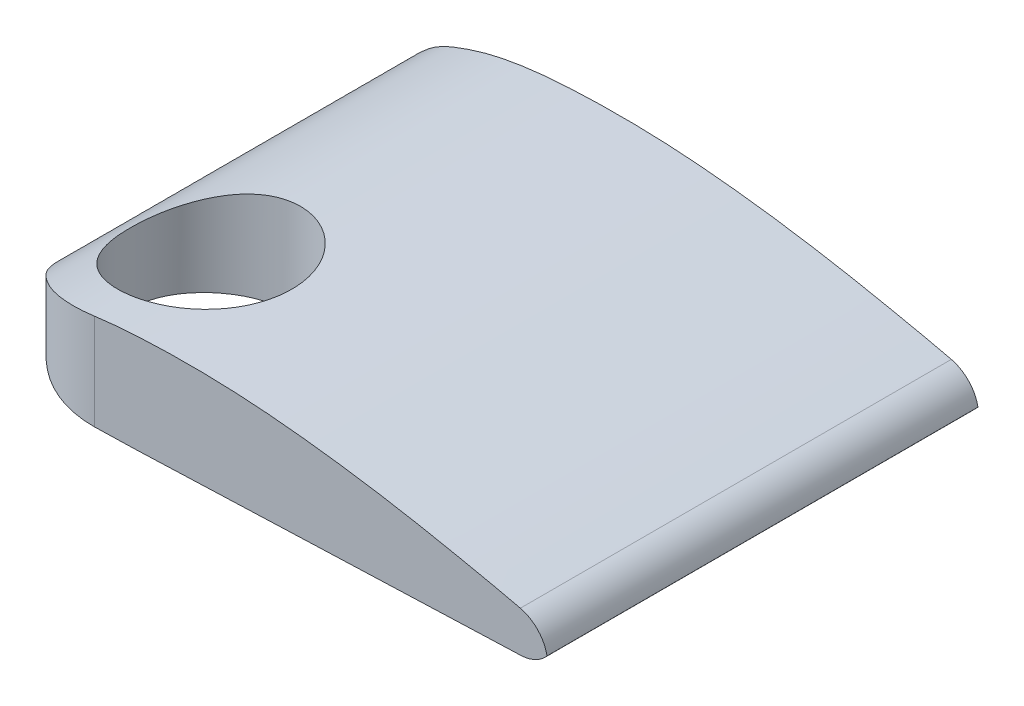
SolidWorks part; units mm, degrees
ref_plane "Ön Düzlem" through (0, 0, 0) normal (0, 0, 1) x (1, 0, 0)
ref_plane "Üst Düzlem" through (0, 0, 0) normal (0, 1, 0) x (1, 0, 0)
ref_plane "Sağ Düzlem" through (0, 0, 0) normal (1, 0, 0) x (0, 0, -1)
sketch "Sketch1" plane through (0, 0, 0) normal (0, 0, 1) x (1, 0, 0)
  line L0 (273.8644, 129.7584) -> (1369.8644, 129.7584) construction
  line L1 (149.8581, 0) -> (149.8558, -0.0087)
  line L2 (155.9643, 3.5657) -> (153.7663, -4.8024)
  spline S0 degree 3 poles (149.8581, 0) (148.0649, 0.471) (143.2248, 1.7424) (133.1757, 3.886) (119.4995, 6.7583) (102.5414, 9.7444) (85.9645, 11.9563) (70.8168, 13.3138) (56.6678, 13.8481) (41.7647, 13.6427) (27.8783, 12.5388) (17.5169, 10.3502) (10.936, 8.1212) (5.6282, 6.0173) (2.2408, 3.1599) (-0.2937, 0.7197) (0.5423, -2.4008) (4.9566, -3.5377) (10.6122, -4.3278) (18.7708, -4.4982) (30.5005, -4.4934) (45.7845, -3.9122) (66.3708, -3.1228) (87.0163, -2.3781) (108.488, -1.5762) (124.5472, -1.0028) (137.7849, -0.5219) (145.1223, -0.2664) (148.9169, -0.06) (149.8558, -0.0087) knots 0 0 0 0 0.018163 0.049023 0.100644 0.15508 0.217678 0.264436 0.304025 0.356345 0.410393 0.440307 0.459596 0.478843 0.494821 0.504999 0.508601 0.524256 0.542616 0.567477 0.602874 0.658123 0.717036 0.804816 0.860487 0.927555 0.96225 0.990269 0.999481 0.999481 0.999481 0.999481
  spline S1 degree 1 poles (155.9643, 3.5657) (153.7663, -4.8024) knots 0 0 1 1 construction
  spline S2 degree 3 poles (155.9643, 3.5657) (154.3789, 3.9821) (151.2214, 4.8106) (146.4053, 6.0796) (141.4592, 7.231) (136.6165, 8.2623) (131.8023, 9.2806) (125.348, 10.622) (117.2296, 12.2227) (107.436, 13.9393) (97.5987, 15.4408) (87.7223, 16.7063) (77.8097, 17.7331) (67.8079, 18.447) (57.7939, 18.7732) (47.7698, 18.7355) (39.4274, 18.4012) (32.6805, 17.8783) (27.5943, 17.2987) (22.4892, 16.4892) (18.2218, 15.5713) (14.817, 14.6458) (12.3108, 13.8604) (9.8671, 13.0078) (7.4153, 12.102) (5.1995, 11.1503) (3.4062, 10.1987) (2.0681, 9.3602) (0.8539, 8.4728) (-0.2716, 7.5539) (-1.1738, 6.7528) (-1.8463, 6.1385) (-2.5103, 5.5088) (-3.2938, 4.6501) (-4.14, 3.4467) (-4.7575, 1.9999) (-5.006, 0.5771) (-5.0045, -0.9474) (-4.6414, -2.46) (-3.865, -4.0582) (-2.7961, -5.3678) (-1.2429, -6.6358) (0.6171, -7.5095) (2.5072, -8.0359) (3.9575, -8.3344) (5.3338, -8.5928) (6.6822, -8.8045) (8.4438, -9.0334) (10.6183, -9.23) (13.2248, -9.3643) (15.8027, -9.4307) (18.317, -9.4626) (21.6435, -9.4888) (25.784, -9.4833) (30.7543, -9.4112) (35.716, -9.2795) (40.6638, -9.1103) (47.2322, -8.8598) (55.417, -8.5465) (65.237, -8.1755) (75.0605, -7.8138) (84.8885, -7.4554) (97.9978, -6.9718) (114.3642, -6.3678) (129.1179, -5.8389) (138.9321, -5.4857) (143.8593, -5.3146) (148.8723, -5.0773) (152.1278, -4.8919) (153.7663, -4.8024) knots -0.016327 -0.016327 -0.016327 -0.016327 -0.000269 0.015789 0.031847 0.047904 0.063962 0.08002 0.112136 0.144252 0.176368 0.208483 0.240599 0.272715 0.304831 0.336947 0.369062 0.38512 0.401178 0.417236 0.433294 0.441323 0.449352 0.457381 0.46541 0.473439 0.477453 0.481468 0.485482 0.489497 0.493511 0.495518 0.497526 0.499533 0.50154 0.503547 0.504551 0.505554 0.507562 0.509569 0.511576 0.513583 0.517598 0.521612 0.525627 0.529641 0.533656 0.53767 0.545699 0.553728 0.561757 0.569786 0.577815 0.593873 0.609931 0.625989 0.642047 0.658105 0.69022 0.722336 0.754452 0.786568 0.818683 0.882915 0.947147 0.963205 0.979262 0.99532 1.011378 1.011378 1.011378 1.011378
  dimension "D1" = 5
extrude "Boss-Extrude1" add sketch "Sketch1" along normal blind 120
sketch "Sketch3" plane through (0, 0, 0) normal (0, 0, -1) x (-1, 0, 0)
  spline S0 degree 3 poles (-11.7419, -7.2673) (10.6267, -4.9516) (-6.4343, 9.3983) (-25.8631, 15.5562) (-57.7636, 15.487) (-93.5429, 14.8992) (-123.4443, 9.4204) (-152.3472, 3.7333) (-149.2242, -5.0274) (-129.7309, -2.6137) (-109.2458, -5.8546) (-71.1466, -4.9504) (-43.1487, -7.1816) (-11.7419, -7.2673) (10.6267, -4.9516) (-6.4343, 9.3983) knots -0.325561 -0.13651 -0.103954 0 0.019859 0.056297 0.104262 0.197907 0.252889 0.30035 0.312342 0.372817 0.481474 0.674439 0.86349 0.896046 1 1.019859 1.056297 1.104262 only from (0.8788, 2.8169) to (0.8788, 2.8169)
sketch "Sketch4" plane through (0, 0, 0) normal (0, 1, 0) x (1, 0, 0)
  line L7 (-4.9986, -120) -> (60.0014, -120)
  line L8 (-4.9986, -120) -> (-4.9986, -55)
  line L9 (-4.9986, -55) -> (60.0014, -55)
  line L10 (60.0014, -120) -> (60.0014, -55)
  circle A1 centre (27.5014, -87.5) radius 22.5
  dimension "D1" = 45
  dimension "D2" = 32.5
  dimension "D3" = 32.5
  dimension "D4" = 65
  dimension "D5" = 65
sketch "Sketch5" plane through (0, 0, 0) normal (0, 0, -1) x (-1, 0, 0)
  line L0 (-16.8432, -9.4426) -> (-66.6079, -9.4426) construction
  spline S0 degree 3 poles (-155.9643, 3.5657) (-154.3789, 3.9821) (-151.2214, 4.8106) (-146.4053, 6.0796) (-141.4592, 7.231) (-136.6165, 8.2623) (-131.8023, 9.2806) (-125.348, 10.622) (-117.2296, 12.2227) (-107.436, 13.9393) (-97.5987, 15.4408) (-87.7223, 16.7063) (-77.8097, 17.7331) (-67.8079, 18.447) (-57.7939, 18.7732) (-47.7698, 18.7355) (-39.4274, 18.4012) (-32.6805, 17.8783) (-27.5943, 17.2987) (-22.4892, 16.4892) (-18.2218, 15.5713) (-14.817, 14.6458) (-12.3108, 13.8604) (-9.8671, 13.0078) (-7.4153, 12.102) (-5.1995, 11.1503) (-3.4062, 10.1987) (-2.0681, 9.3602) (-0.8539, 8.4728) (0.2716, 7.5539) (1.1738, 6.7528) (1.8463, 6.1385) (2.5103, 5.5088) (3.2938, 4.6501) (4.14, 3.4467) (4.7575, 1.9999) (5.006, 0.5771) (5.0045, -0.9474) (4.6414, -2.46) (3.865, -4.0582) (2.7961, -5.3678) (1.2429, -6.6358) (-0.6171, -7.5095) (-2.5072, -8.0359) (-3.9575, -8.3344) (-5.3338, -8.5928) (-6.6822, -8.8045) (-8.4438, -9.0334) (-10.6183, -9.23) (-13.2248, -9.3643) (-15.8027, -9.4307) (-18.317, -9.4626) (-21.6435, -9.4888) (-25.784, -9.4833) (-30.7543, -9.4112) (-35.716, -9.2795) (-40.6638, -9.1103) (-47.2322, -8.8598) (-55.417, -8.5465) (-65.237, -8.1755) (-75.0605, -7.8138) (-84.8885, -7.4554) (-97.9978, -6.9718) (-114.3642, -6.3678) (-129.1179, -5.8389) (-138.9321, -5.4857) (-143.8593, -5.3146) (-148.8723, -5.0773) (-152.1278, -4.8919) (-153.7663, -4.8024) knots -0.016327 -0.016327 -0.016327 -0.016327 -0.000269 0.015789 0.031847 0.047904 0.063962 0.08002 0.112136 0.144252 0.176368 0.208483 0.240599 0.272715 0.304831 0.336947 0.369062 0.38512 0.401178 0.417236 0.433294 0.441323 0.449352 0.457381 0.46541 0.473439 0.477453 0.481468 0.485482 0.489497 0.493511 0.495518 0.497526 0.499533 0.50154 0.503547 0.504551 0.505554 0.507562 0.509569 0.511576 0.513583 0.517598 0.521612 0.525627 0.529641 0.533656 0.53767 0.545699 0.553728 0.561757 0.569786 0.577815 0.593873 0.609931 0.625989 0.642047 0.658105 0.69022 0.722336 0.754452 0.786568 0.818683 0.882915 0.947147 0.963205 0.979262 0.99532 1.011378 1.011378 1.011378 1.011378 construction
fillet "Fillet1" radius 10 2 edges at (153.7663, -4.8024, 60) (155.9643, 3.5657, 60)
extrude "Boss-Extrude2" add sketch "Sketch4" along normal up to next and the other way up to next
extrude "Cut-Extrude1" cut sketch "Sketch4<4>" along normal blind 49 and the other way blind 51 contours A1 region at (27.5014, 0, 87.5)
sketch "Sketch4<4>" plane through (0, 0, 0) normal (0, 1, 0) x (1, 0, 0) same geometry as "Sketch4"
extrude "Boss-Extrude3" add sketch "Sketch3" along normal blind 10 from surface starting at face at (149.1615, 1.7482, 120)
sketch "Sketch7" plane through (0, 0, 0) normal (0, 1, 0) x (1, 0, 0)
  line L0 (-4.9986, -87.5) -> (-4.9986, -120)
  line L1 (-4.9986, -120) -> (27.5014, -120)
  arc A0 (-4.9986, -87.5) -> (27.5014, -120) centre (27.5014, -87.5) ccw
extrude "Cut-Extrude3" cut sketch "Sketch7" against normal blind 20 and the other way blind 24
